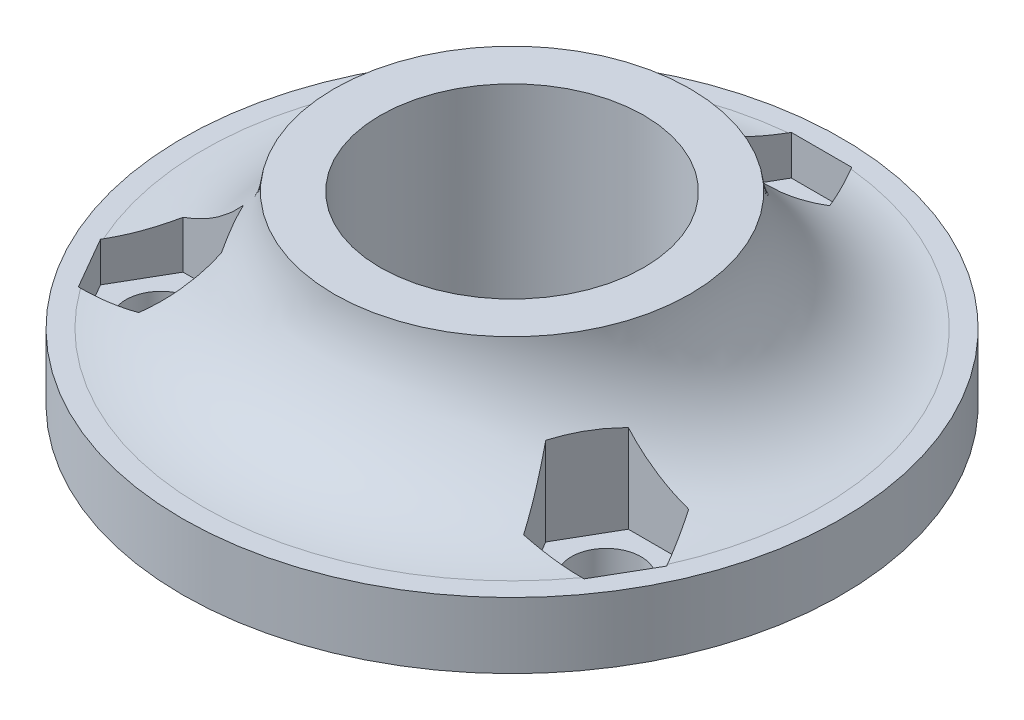
SolidWorks part; units mm, degrees
ref_plane "Alzado" through (0, 0, 0) normal (0, 0, 1) x (1, 0, 0)
ref_plane "Planta" through (0, 0, 0) normal (0, 1, 0) x (1, 0, 0)
ref_plane "Vista lateral" through (0, 0, 0) normal (1, 0, 0) x (0, 0, -1)
sketch "Sketch1" plane through (0, 0, 0) normal (0, 1, 0) x (1, 0, 0)
  circle A0 centre (0, 0) radius 25
  circle A1 centre (0, 0) radius 10
  dimension "D1" = 20
  dimension "D2" = 50
extrude "Boss-Extrude1" add sketch "Sketch1" along normal blind 5
sketch "Sketch3" plane through (0, 5, 0) normal (0, 1, 0) x (1, 0, 0)
  line L1 (4.5842, 19.5) -> (2.2921, 23.47)
  line L2 (2.2921, 23.47) -> (-2.2921, 23.47)
  line L3 (-2.2921, 23.47) -> (-4.5842, 19.5)
  line L4 (-4.5842, 19.5) -> (-2.2921, 15.53)
  line L5 (-2.2921, 15.53) -> (2.2921, 15.53)
  line L6 (2.2921, 15.53) -> (4.5842, 19.5)
  circle A0 centre (0, 0) radius 19.5 construction
  circle A1 centre (0, 19.5) radius 3.97 construction
  dimension "D1" = 39
  dimension "D2" = 7.94
extrude "Cut-Extrude1" cut sketch "Sketch3" against normal blind 3
sketch "Sketch4" plane through (0, 2, 0) normal (0, 1, 0) x (1, 0, 0)
  circle A0 centre (0, 19.5) radius 2.65
  dimension "D1" = 5.3
extrude "Cut-Extrude2" cut sketch "Sketch4" against normal through all
pattern_circular "CirPattern1" count 3 over 360 about axis through (0, 5, 0) along (0, -1, 0) of "Cut-Extrude1", "Cut-Extrude2" reverse direction yes
sketch "Sketch6" plane through (0, 0, 0) normal (0, 1, 0) x (1, 0, 0)
  circle A0 centre (0, 0) radius 10
  circle A1 centre (0, 0) radius 13.5
  circle A2 centre (0, 0) radius 10 construction
  dimension "D1" = 27
extrude "Boss-Extrude2" add sketch "Sketch6" along normal blind 14
fillet "Fillet1" radius 10 1 edges at (0, 5, 13.5)
sketch "Sketch7" plane through (0, 0, 0) normal (0, -1, 0) x (1, 0, 0)
  circle A1 centre (0, 0) radius 10
  circle A2 centre (0, 0) radius 13.15
  circle A3 centre (0, 0) radius 10 construction
  dimension "D1" = 26.3
extrude "Boss-Extrude3" add sketch "Sketch7" along normal blind 1.45
